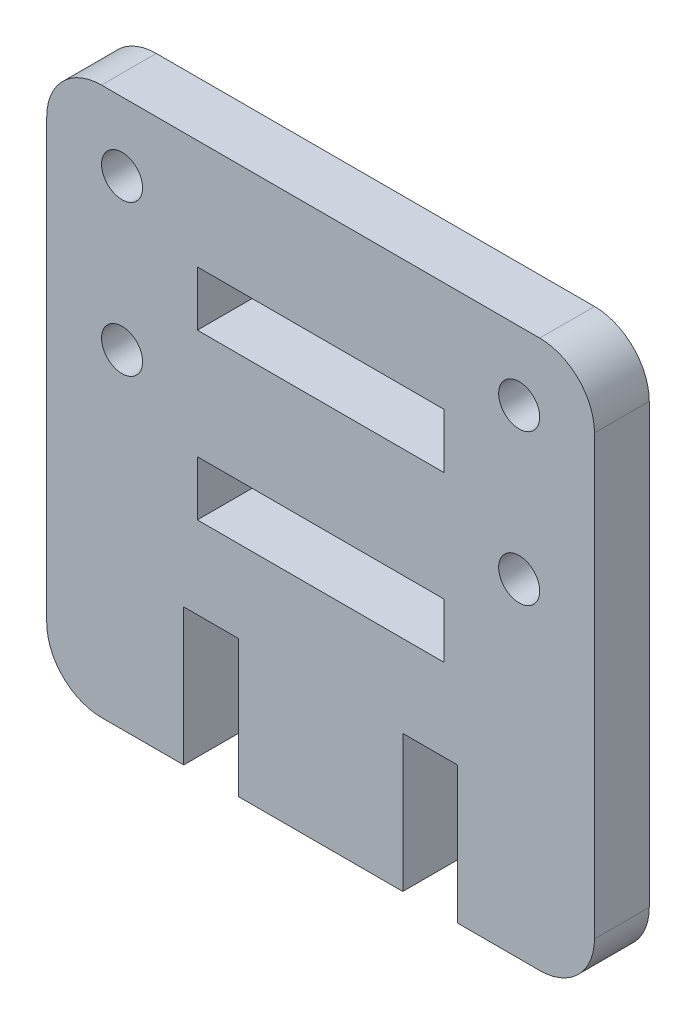
SolidWorks part; units mm, degrees
material "Acrylic (Medium-high impact)"
ref_plane "Front Plane" through (0, 0, 0) normal (0, 0, 1) x (1, 0, 0)
ref_plane "Top Plane" through (0, 0, 0) normal (0, 1, 0) x (1, 0, 0)
ref_plane "Right Plane" through (0, 0, 0) normal (1, 0, 0) x (0, 0, -1)
sketch "Model" plane through (0, 0, 0) normal (0, 0, 1) x (1, 0, 0)
  line L0 (2, 0) -> (5, 0)
  line L1 (5, 0) -> (5, 5)
  line L2 (5, 5) -> (7, 5)
  line L3 (7, 5) -> (7, 0)
  line L4 (7, 0) -> (13, 0)
  line L5 (13, 0) -> (13, 5)
  line L6 (13, 5) -> (15, 5)
  line L7 (15, 5) -> (15, 0)
  line L8 (15, 0) -> (18, 0)
  line L9 (0, 2) -> (0, 18)
  line L10 (2, 20) -> (18, 20)
  line L11 (20, 18) -> (20, 2)
  line L12 (5.5, 10) -> (14.5, 10)
  line L13 (14.5, 10) -> (14.5, 8)
  line L15 (5.5, 8) -> (14.5, 8)
  line L16 (5.5, 8) -> (5.5, 10)
  line L17 (5.5, 14) -> (14.5, 14)
  line L18 (14.5, 14) -> (14.5, 16)
  line L19 (14.5, 16) -> (5.5, 16)
  line L20 (5.5, 16) -> (5.5, 14)
  circle A0 centre (2.75, 17.5) radius 0.75
  circle A1 centre (2.75, 12) radius 0.75
  circle A2 centre (17.25, 12) radius 0.75
  circle A3 centre (17.25, 17.5) radius 0.75
  arc A4 (0, 18) -> (2, 20) centre (2, 18) cw
  arc A5 (2, 0) -> (0, 2) centre (2, 2) cw
  arc A6 (20, 2) -> (18, 0) centre (18, 2) cw
  arc A7 (18, 20) -> (20, 18) centre (18, 18) cw
  dimension "D1" = 1.5
  dimension "D2" = 2
  dimension "D3" = 20
  dimension "D4" = 2.75
  dimension "D5" = 2.25
  dimension "D6" = 0.5
  dimension "D7" = 1.5
  dimension "D8" = 1.5
  dimension "D9" = 2.25
  dimension "D10" = 5
  dimension "D11" = 3
  dimension "D12" = 2
  dimension "D13" = 1.5
other "AlignGroup1"
other "AlignGroup2"
other "AlignGroup3"
other "AlignGroup4"
other "AlignGroup5"
other "AlignGroup6"
other "AlignGroup7"
other "AlignGroup8"
extrude "Boss-Extrude1" add sketch "Model" along normal blind 2
